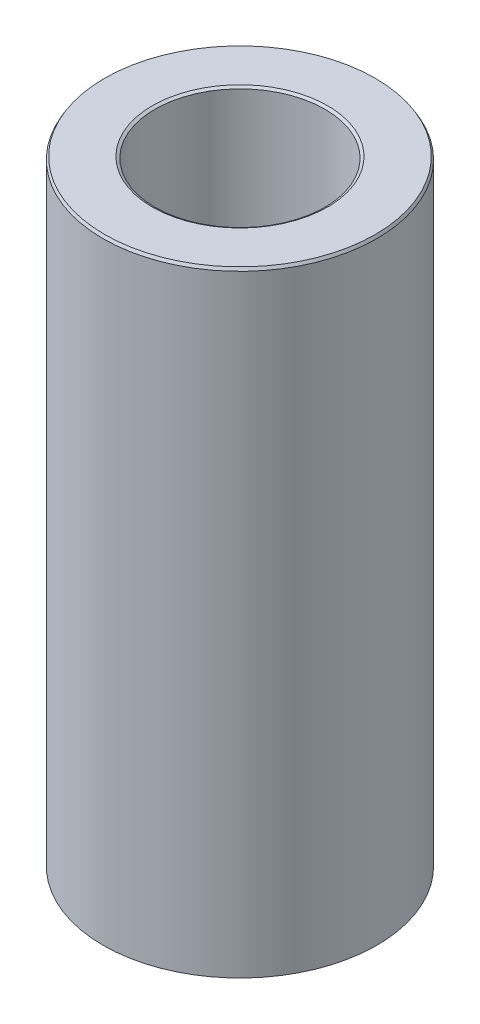
SolidWorks part; units mm, degrees
ref_plane "Front Plane" through (0, 0, 0) normal (0, 0, 1) x (1, 0, 0)
ref_plane "Top Plane" through (0, 0, 0) normal (0, 1, 0) x (1, 0, 0)
ref_plane "Right Plane" through (0, 0, 0) normal (1, 0, 0) x (0, 0, -1)
sketch "Sketch1" plane through (0, 0, 0) normal (0, 1, 0) x (1, 0, 0)
  circle A0 centre (0, 0) radius 60
  dimension "SLEEVE_OD" = 120
extrude "Boss-Extrude1" add sketch "Sketch1" along normal blind 270.1041
sketch "Sketch2" plane through (0, 0, 0) normal (0, 1, 0) x (1, 0, 0)
  circle A0 centre (0, 0) radius 37.2316
  dimension "BORE_D" = 74.4632
extrude "Cut-Extrude1" cut sketch "Sketch2" along normal through all
chamfer "Chamfer1" distance 1.215 angle 30 4 edges at (0, 270.1041, 37.2316) (0, 0, 37.2316) (0, 0, 60) (0, 270.1041, 60) first distance on face at (0, 270.1041, 37.2316) first distance on face at (0, 0, 37.2316) first distance on face at (0, 270.1041, 60)
